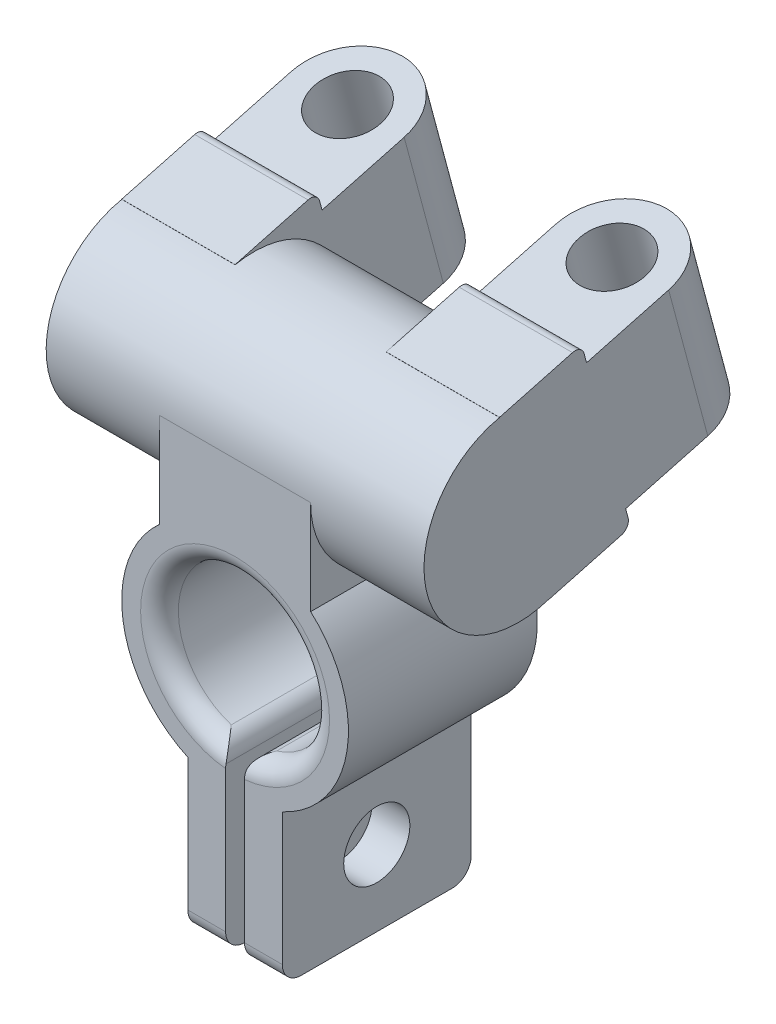
SolidWorks part; units mm, degrees
ref_plane "前视基准面" through (0, 0, 0) normal (0, 0, 1) x (1, 0, 0)
ref_plane "上视基准面" through (0, 0, 0) normal (0, 1, 0) x (1, 0, 0)
ref_plane "右视基准面" through (0, 0, 0) normal (1, 0, 0) x (0, 0, -1)
sketch "草图1" plane through (0, 0, 0) normal (0, 0, 1) x (1, 0, 0)
  line L0 (0, 9.8082) -> (0, -13.4551) construction
  line L1 (-2.5, -5.4544) -> (-2.5, -13.4544)
  line L2 (-2.5, -13.4544) -> (-0.5, -13.4544)
  line L3 (2.5, -13.4544) -> (2.5, -5.4544)
  line L4 (-0.5, -13.4544) -> (-0.5, -3.9686)
  line L5 (0.5, -13.4544) -> (0.5, -3.9686)
  line L6 (0.5, -13.4544) -> (2.5, -13.4544)
  arc A0 (0.5, -3.9686) -> (-0.5, -3.9686) centre (0, 0) ccw
  arc A1 (2.5, -5.4544) -> (-2.5, -5.4544) centre (0, 0) ccw
  dimension "D1" = 8
  dimension "D2" = 12
  dimension "D3" = 0.5
  dimension "D4" = 5
  dimension "D5" = 2.5
  dimension "D6" = 8
extrude "凸台-拉伸1" add sketch "草图1" along normal blind 10
sketch "草图2" plane through (-2.5, 0, 0) normal (-1, 0, 0) x (0, 0, 1)
  line L0 (-3.7457, -9.4544) -> (9.3001, -9.4544) construction
  line L1 (5, -11.5252) -> (5, -0.7817) construction
  line L2 (0, -5.4544) -> (0, -13.4544) construction
  line L3 (10, -5.4544) -> (0, -5.4544) construction
  circle A0 centre (5, -9.4544) radius 1.75
  dimension "D1" = 3.5
  dimension "D2" = 5
  dimension "D3" = 4
extrude "切除-拉伸1" cut sketch "草图2" against normal through all
sketch "草图3" plane through (0, 0, 0) normal (0, 0, 1) x (1, 0, 0)
  line L0 (0, -14.2812) -> (0, 13.2924) construction
  line L1 (-4, 4.4721) -> (-4, 10.4721)
  line L2 (-4, 10.4721) -> (4, 10.4721)
  line L3 (4, 4.4721) -> (4, 10.4721)
  arc A0 (2.5, -5.4544) -> (-2.5, -5.4544) centre (0, 0) ccw construction
  arc A1 (4, 4.4721) -> (-4, 4.4721) centre (0, 0) ccw
  point P10 (0, 10.4721)
  dimension "D1" = 8
  dimension "D2" = 6
extrude "凸台-拉伸2" add sketch "草图3" along normal blind 10
sketch "草图4" plane through (0, 0, 0) normal (1, 0, 0) x (0, 0, -1)
  line L0 (-2.656, 9.4721) -> (-7.344, 9.4721) construction
  line L1 (-5, 13.3584) -> (-5, 0) construction
  line L2 (-10, 10.4721) -> (-10, 4.4721) construction
  line L3 (-10, 4.4721) -> (0, 4.4721) construction
  circle A0 centre (-5, 9.4721) radius 5
  dimension "D1" = 5
  dimension "D2" = 10
  dimension "D3" = 5
extrude "凸台-拉伸3" add sketch "草图4" along normal blind 10 and the other way blind 10
sketch "草图5" plane through (-10, 0, 0) normal (-1, 0, 0) x (0, 0, 1)
  line L0 (0, 9.4721) -> (0, 15.0221)
  line L1 (0, 15.0221) -> (10, 15.0221)
  line L2 (10, 15.0221) -> (10, 9.4721)
  circle A2 centre (5, 9.4721) radius 5 construction
  arc A3 (10, 9.4721) -> (0, 9.4721) centre (5, 9.4721) ccw
  dimension "D1" = 5.55
extrude "切除-拉伸2" cut sketch "草图5" against normal through all both and the other way through all
sketch "草图6" plane through (10, 0, 0) normal (1, 0, 0) x (0, 0, -1)
  line L0 (-4.7065, 9.5508) -> (6.8846, 12.6566) construction
  line L1 (-5, 14.7884) -> (-5, -1.0626) construction
  line L2 (-2.3267, 7.9462) -> (6.002, 10.1778) construction
  line L3 (-6.0006, 14.3804) -> (5.5905, 17.4862)
  line L4 (-3.4124, 4.7212) -> (8.1787, 7.827)
  line L5 (-6.0006, 14.3804) -> (-3.4124, 4.7212) construction
  line L6 (5.5905, 17.4862) -> (8.1787, 7.827)
  line L7 (-6.0006, 14.3804) -> (-3.4124, 4.7212)
  line L8 (-4.7065, 9.5508) -> (11.5617, 9.5508) construction
  circle A0 centre (-5, 9.4721) radius 5 construction
  dimension "D1" = 15
  dimension "D3" = 12
extrude "凸台-拉伸4" add sketch "草图6" against normal blind 6
sketch "草图7" plane through (0, 14.9173, 3.9971) normal (0, 0.9659, 0.2588) x (1, 0, 0)
  line L0 (7, 15.0516) -> (7, -3.4998) construction
  line L1 (4, 9.9258) -> (10, 9.9258) construction
  line L2 (4, 6.9258) -> (4, 9.9258)
  line L3 (4, 9.9258) -> (10, 9.9258)
  line L4 (10, 9.9258) -> (10, 6.9258)
  arc A0 (10, 6.9258) -> (4, 6.9258) centre (7, 6.9258) ccw
  line M2 (4, 9.9258) -> (4, -2.0742)
  line M5 (10, -2.0742) -> (10, 9.9258)
  line M6 (10, 9.9258) -> (4, 9.9258)
extrude "切除-拉伸3" cut sketch "草图7" against normal blind 10 contours A0 L3 M2 | A0 M5 M6 region at (9.3299, 17.3128, -4.9432) region at (4.6701, 17.3128, -4.9432)
sketch "草图8" plane through (10, 0, 0) normal (1, 0, 0) x (0, 0, -1)
  line L0 (5.0234, 12.1579) -> (-6.7403, 9.0058) construction
  line L1 (5.5905, 17.4862) -> (-1.6539, 15.5451)
  line L2 (2.6927, 16.7098) -> (-6.0006, 14.3804) construction
  line L3 (-1.6539, 15.5451) -> (-1.3951, 14.5792)
  line L4 (-1.3951, 14.5792) -> (5.8493, 16.5203)
  line L5 (5.8493, 16.5203) -> (5.5905, 17.4862)
  line L6 (0.9343, 5.8858) -> (0.6754, 6.8518)
  line L7 (7.9199, 8.7929) -> (8.1787, 7.827)
  line L8 (8.1787, 7.827) -> (0.9343, 5.8858)
  line L9 (0.6754, 6.8518) -> (7.9199, 8.7929)
  dimension "D1" = 1
  dimension "D2" = 5
extrude "切除-拉伸4" cut sketch "草图8" against normal through all both and the other way through all
sketch "草图9" plane through (0, 13.9513, 3.7382) normal (0, 0.9659, 0.2588) x (1, 0, 0)
  line L0 (12.4399, 6.9258) -> (2.4329, 6.9258) construction
  circle A0 centre (7, 6.9258) radius 1.75
  dimension "D1" = 3.5
extrude "切除-拉伸5" cut sketch "草图9" against normal up to next
fillet "圆角2" radius 0.5 2 edges at (7, 5.8858, -0.9343) (7, 15.5451, 1.6539)
mirror "镜向4" about plane through (0, 0, 0) normal (1, 0, 0) of "凸台-拉伸4", "切除-拉伸4", "切除-拉伸5", "凸台-拉伸3", "切除-拉伸3", "圆角2"
fillet "圆角3" radius 1 8 edges at (-0.5, -3.9686, 5) (0, 4, 10) (0.5, -3.9686, 5) (0, 4, 0) (1.5, -13.4544, 10) (1.5, -13.4544, 0) (-1.5, -13.4544, 0) (-1.5, -13.4544, 10)
